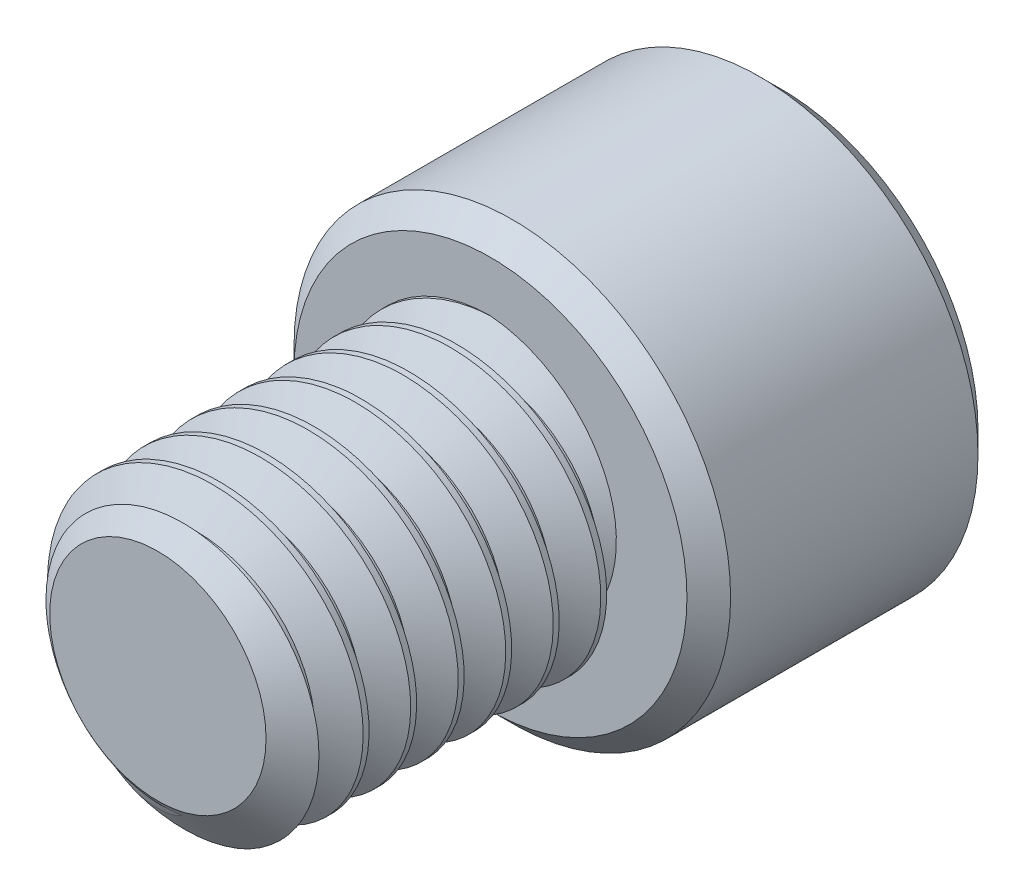
SolidWorks part; units mm, degrees
ref_plane "Front Plane" through (0, 0, 0) normal (0, 0, 1) x (1, 0, 0)
ref_plane "Top Plane" through (0, 0, 0) normal (0, 1, 0) x (1, 0, 0)
ref_plane "Right Plane" through (0, 0, 0) normal (1, 0, 0) x (0, 0, -1)
sketch "Sketch1" plane through (0, 0, 0) normal (0, 0, 1) x (1, 0, 0)
  circle A0 centre (0, 0) radius 5.5626
  dimension "OD" = 11.1252
extrude "Extrude1" add sketch "Sketch1" against normal blind 12.7
sketch "Sketch2" plane through (0, 0, 0) normal (0, 0, 1) x (1, 0, 0)
  circle A0 centre (0, 0) radius 5.5626 construction
  circle A1 centre (0, 0) radius 5.5626
curve "Helix/Spiral1" pitch 1.8143 height 14.5143 turns 8 parameters "pitch"=1.8143
sketch "Sketch3" plane through (0, 0, 0) normal (1, 0, 0) x (0, 0, -1)
  line L0 (-1.5875, 5.5626) -> (-0.9071, 4.3842)
  line L1 (-0.9071, 4.3842) -> (-0.6804, 4.3842)
  line L2 (-0.6804, 4.3842) -> (0, 5.5626)
  line L3 (-1.5875, 5.5626) -> (0, 5.5626)
  line L4 (-0.7938, 5.5626) -> (-0.7938, 4.3842) construction
  line L5 (-1.2473, 4.9734) -> (-0.3402, 4.9734) construction
  line L6 (0, 5.5626) -> (0, -5.5626) construction
  dimension "D1" = 0.2268
  dimension "D2" = 0.9071
  dimension "D3" = 60
sweep "Cut-Sweep1" cut profiles "Sketch3" path "Helix/Spiral1"
sketch "Sketch4" plane through (0, 0, 0) normal (1, 0, 0) x (0, 0, -1)
  line L0 (1.003, 5.5626) -> (0, 4.1302)
  line L1 (0, 4.1302) -> (0, 5.5626)
  line L2 (1.003, 5.5626) -> (0, 5.5626)
  line L3 (-1.5875, 5.5626) -> (0, 5.5626) construction
  line L4 (0, 0) -> (7.0209, 0) construction
  dimension "D1" = 55
  dimension "D2" = 0.254
revolve "Cut-Revolve1" cut sketch "Sketch4" angle 360 about L4
sketch "Sketch5" plane through (0, 0, 0) normal (1, 0, 0) x (0, 0, -1)
  line L0 (12.7, -4.4088) -> (12.7, 3.9691) construction
  line L1 (12.7, 5.6896) -> (87.4665, 5.6896)
  line L2 (12.7, 5.6896) -> (12.7, 0)
  line L3 (12.7, 0) -> (87.3125, 0)
  line L4 (87.3125, 5.3594) -> (87.3125, 0)
  line L5 (87.4665, 5.6896) -> (87.3125, 5.3594)
  line L6 (0, 0) -> (9.9695, 0) construction
  point P3 (87.3125, 5.6896)
  point P10 (87.3125, 5.6896)
  dimension "D1" = 0.3302
  dimension "Thread min" = 87.3125
  dimension "D2" = 0.127
  dimension "D3" = 25
revolve "partially thread" add sketch "Sketch5" angle 360 about L6
sketch "Sketch6" plane through (0, 0, -12.7) normal (0, 0, -1) x (-1, 0, 0)
  circle A0 centre (0, 0) radius 8.3344
  dimension "head dia" = 16.6687
extrude "Extrude2" add sketch "Sketch6" along normal blind 11.1125
sketch "Sketch7" plane through (0, 0, -23.8125) normal (0, 0, -1) x (-1, 0, 0)
  line L1 (0, 5.4993) -> (-4.7625, 2.7496)
  line L2 (-4.7625, 2.7496) -> (-4.7625, -2.7496)
  line L3 (-4.7625, -2.7496) -> (0, -5.4993)
  line L4 (0, -5.4993) -> (4.7625, -2.7496)
  line L5 (4.7625, -2.7496) -> (4.7625, 2.7496)
  line L6 (4.7625, 2.7496) -> (0, 5.4993)
  circle A0 centre (0, 0) radius 4.7625 construction
  dimension "hex dia" = 9.525
extrude "Cut-Extrude1" cut sketch "Sketch7" against normal blind 7.1438
sketch "Sketch8" plane through (0, 0, -23.8125) normal (0, 0, -1) x (-1, 0, 0)
  circle A0 centre (0, 0) radius 5.4993
extrude "Cut-Extrude2" cut sketch "Sketch8" against normal through all draft 45
chamfer "Chamfer1" distance 0.8334 angle 45 2 edges at (-8.3344, 0, -23.8125) (-8.3344, 0, -12.7)
sketch "Sketch9" plane through (0, 0, 0) normal (1, 0, 0) x (0, 0, -1)
  line L0 (0, 5.5626) -> (0, -5.5626) construction
  line L1 (9.9786, 5.5626) -> (9.9786, -5.5626) construction
  dimension "D1" = 9.9786
  dimension "D4" = 0.635
  dimension "D5" = 0.3302
equation "\"D3@Helix/Spiral1\" = \"screw length@Extrude1\"+\"pitch@Helix/Spiral1\""
equation "\"D1@Sketch3\" = \"pitch@Helix/Spiral1\"*.125"
equation "\"D2@Sketch3\" = \"pitch@Helix/Spiral1\"*.5"
equation "\"D1@Cut-Extrude1\" = \"hex dia@Sketch7\"*.75"
equation "\"D1@Chamfer1\" = \"head dia@Sketch6\"*.05"
equation "\"D1@Sketch9\" = \"pitch@Helix/Spiral1\"*5.5"
